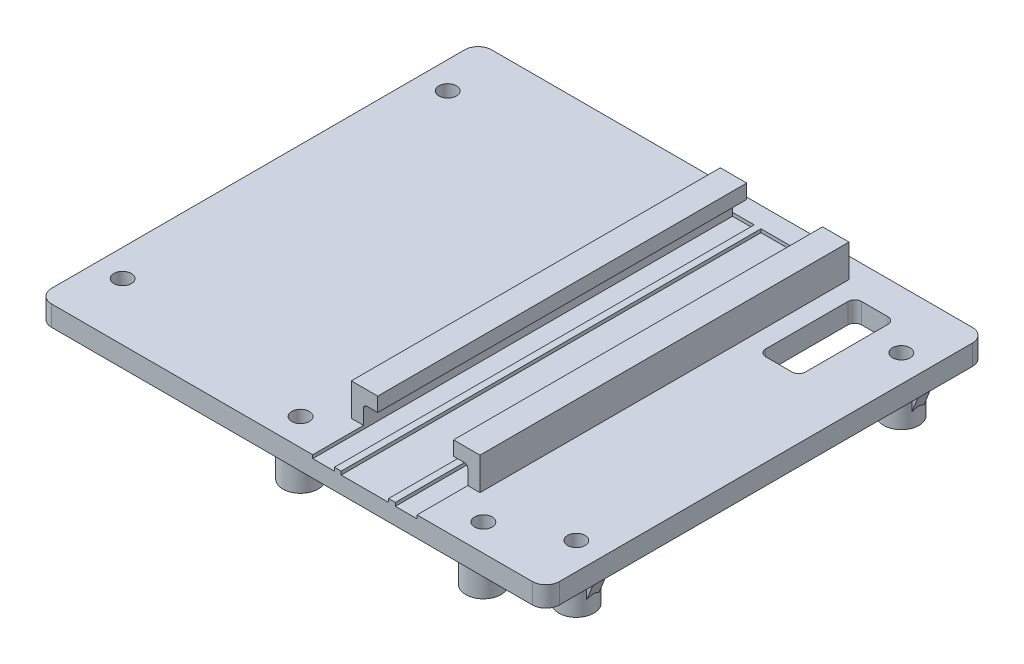
SolidWorks part; units mm, degrees
ref_plane "Alzado" through (0, 0, 0) normal (0, 0, 1) x (1, 0, 0)
ref_plane "Planta" through (0, 0, 0) normal (0, 1, 0) x (1, 0, 0)
ref_plane "Vista lateral" through (0, 0, 0) normal (1, 0, 0) x (0, 0, -1)
sketch "Croquis9" plane through (0, 0, 0) normal (0, 0, 1) x (1, 0, 0)
  line L0 (0, 17.7123) -> (0, -23.4478) construction
  line L1 (0, 10.708) -> (-22, 10.708)
  line L2 (-22, 10.708) -> (-22, 7.708)
  line L3 (-22, 7.708) -> (-19, 7.708)
  line L4 (-19, 7.708) -> (-4.5, 6.708)
  line L5 (-4.5, 6.708) -> (-4.5, -1.292)
  line L6 (-4.5, -1.292) -> (0, -1.292)
  line L7 (0, 10.708) -> (0, -1.292)
  dimension "D1" = 22
  dimension "D2" = 4.5
  dimension "D3" = 3
  dimension "D4" = 1
  dimension "D5" = 8
  dimension "D6" = 3
  dimension "D7" = 12
revolve "Revolución3" add sketch "Croquis9" angle 360 about L0
sketch "Croquis17" plane through (0, 0, 0) normal (1, 0, 0) x (0, 0, -1)
  line L0 (-4.5, -1.292) -> (4.5, -1.292) construction
  circle A0 centre (0, 4.708) radius 1.5
  dimension "D1" = 3
  dimension "D2" = 6
extrude "Cortar-Extruir7" cut sketch "Croquis17" along normal up to next
sketch "Croquis18" plane through (0, 10.708, 0) normal (0, 1, 0) x (1, 0, 0)
  line L0 (1, 2.9343) -> (1, -2.9343)
  arc A0 (1, 2.9343) -> (1, -2.9343) centre (0, 0) ccw
  dimension "D1" = 6.2
  dimension "D2" = 1
extrude "Cortar-Extruir10" cut sketch "Croquis18" against normal blind 6 from offset 3 offset against normal yes
sketch "Croquis21" plane through (0, 0, 0) normal (0, 0, 1) x (1, 0, 0)
  line L0 (0, 3.5811) -> (0, -1.3759) construction
  line L1 (0, 1.8085) -> (-3.1, 1.8085)
  line L2 (-3.1, 1.8085) -> (-3.1, -1.6716)
  line L3 (-3.1, -1.6716) -> (0, -1.6716)
  line L4 (0, 1.8085) -> (0, -1.6716)
  dimension "D1" = 3.1
revolve "Cortar-Revolución1" cut sketch "Croquis21" angle 360 about L0
chamfer "Chaflán2" distance 0.5 angle 45 1 edges at (1, 1.8085, 0)
chamfer "Chaflán1" [suppressed] distance 0.5 angle 45
sketch "Croquis22" plane through (0, 10.708, 0) normal (0, 1, 0) x (1, 0, 0)
  line L1 (-37.5, -32.5) -> (37.5, -32.5)
  line L2 (-37.5, -32.5) -> (-37.5, 32.5)
  line L3 (-37.5, 32.5) -> (37.5, 32.5)
  line L4 (37.5, -32.5) -> (37.5, 32.5)
  line L5 (-37.5, -32.5) -> (37.5, 32.5) construction
  line L6 (-37.5, 32.5) -> (37.5, -32.5) construction
  point P0 (0, 0)
  dimension "D1" = 65
  dimension "D2" = 75
extrude "Saliente-Extruir1" add sketch "Croquis22" against normal up to surface (3 mm away) up to face at (0, 7.708, 19)
fillet "Redondeo1" radius 2 4 edges at (-37.5, 9.208, -32.5) (37.5, 9.208, -32.5) (37.5, 9.208, 32.5) (-37.5, 9.208, 32.5)
sketch "Croquis23" plane through (0, 10.708, 0) normal (0, 1, 0) x (1, 0, 0)
  circle A0 centre (-33.5, 24) radius 1.3
  circle A1 centre (-33.5, -24) radius 1.3
  circle A2 centre (33.5, -24) radius 1.3
  circle A3 centre (33.5, 24) radius 1.3
  dimension "D1" = 2.6
  dimension "D4" = 48
  dimension "D3" = 33.5
  dimension "D2" = 67
  dimension "D5" = 24
extrude "Cortar-Extruir11" cut sketch "Croquis23" against normal blind 2
sketch "Croquis24" plane through (0, 10.708, 0) normal (0, 1, 0) x (1, 0, 0)
  line L1 (3.27, 29.5) -> (18.27, 29.5)
  line L2 (3.27, 29.5) -> (3.27, -32.5)
  line L3 (3.27, -32.5) -> (18.27, -32.5)
  line L4 (18.27, 29.5) -> (18.27, -32.5)
  line L5 (6.27, 29.5) -> (7.27, 29.5)
  line L6 (6.27, 29.5) -> (6.27, -32.5)
  line L7 (6.27, -32.5) -> (7.27, -32.5)
  line L8 (7.27, 29.5) -> (7.27, -32.5)
  line L9 (14.27, 29.5) -> (15.27, 29.5)
  line L10 (14.27, 29.5) -> (14.27, -32.5)
  line L11 (14.27, -32.5) -> (15.27, -32.5)
  line L12 (15.27, 29.5) -> (15.27, -32.5)
  line L13 (35.5, 32.5) -> (-35.5, 32.5) construction
  line L14 (-35.5, -32.5) -> (35.5, -32.5) construction
  dimension "D1" = 3
  dimension "D2" = 15
  dimension "D3" = 1
  dimension "D4" = 1
  dimension "D5" = 3.27
  dimension "D6" = 3
  dimension "D7" = 3
extrude "Cortar-Extruir12" cut sketch "Croquis24" against normal blind 0.5 contours L6 L1 L2 L3 | L10 L1 L8 L3 | L1 L12 L3 L4 region at (4.77, 10.708, 1.5) region at (10.77, 10.708, 1.5) region at (16.77, 10.708, 1.5)
sketch "Croquis25" plane through (0, 10.708, 0) normal (0, 1, 0) x (1, 0, 0)
  line L0 (3.27, 29.5) -> (3.27, -32.5) construction
  line L1 (18.27, 29.5) -> (18.27, -32.5) construction
  line L3 (-35.5, -32.5) -> (3.27, -32.5) construction
  circle A0 centre (-2.73, -28.5) radius 1.3
  circle A1 centre (24.27, -28.5) radius 1.3
  circle A2 centre (33.5, -24) radius 1.3 construction
  circle A3 centre (33.5, -24) radius 1.3 construction
  dimension "D2" = 6
  dimension "D1" = 6
  dimension "D4" = 4
extrude "Cortar-Extruir13" cut sketch "Croquis25" against normal blind 2
sketch "Croquis26" plane through (0, 10.708, 0) normal (0, 1, 0) x (1, 0, 0)
  line L1 (22.988, 27.6308) -> (28.8765, 27.6308)
  line L2 (22.988, 27.6308) -> (22.988, 13.4757)
  line L3 (22.988, 13.4757) -> (28.8765, 13.4757)
  line L4 (28.8765, 27.6308) -> (28.8765, 13.4757)
extrude "Cortar-Extruir14" cut sketch "Croquis26" against normal blind 10
sketch "Croquis30" plane through (0, 0, 32.5) normal (0, 0, 1) x (1, 0, 0)
  line L0 (3.27, 10.708) -> (1.27, 10.708)
  line L1 (1.27, 10.708) -> (1.27, 15.508)
  line L2 (1.27, 15.508) -> (5.17, 15.508)
  line L3 (5.17, 15.508) -> (5.17, 13.408)
  line L4 (5.17, 13.408) -> (3.27, 13.408)
  line L5 (3.27, 13.408) -> (3.27, 10.708)
  line L6 (18.27, 10.708) -> (20.27, 10.708)
  line L7 (18.27, 10.708) -> (35.5, 10.708) construction
  line L8 (20.27, 10.708) -> (20.27, 15.508)
  line L9 (20.27, 15.508) -> (16.37, 15.508)
  line L10 (16.37, 15.508) -> (16.37, 13.408)
  line L11 (16.37, 13.408) -> (18.27, 13.408)
  line L12 (18.27, 13.408) -> (18.27, 10.708)
  dimension "D1" = 1.9
  dimension "D2" = 4.8
  dimension "D3" = 2
  dimension "D4" = 2.7
extrude "Saliente-Extruir2" add sketch "Croquis30" against normal up to surface (62 mm away) from offset 7.5 up to face at (4.77, 10.458, -29.5) offset against normal yes
sketch "Croquis31" plane through (0, 0, 32.5) normal (0, 0, 1) x (1, 0, 0)
  line L0 (3.27, 13.408) -> (5.17, 13.408) construction
  line L1 (3.27, 10.208) -> (3.07, 10.208)
  line L2 (3.27, 10.208) -> (3.27, 13.408)
  line L3 (3.27, 13.408) -> (3.07, 13.408)
  line L4 (3.07, 10.208) -> (3.07, 13.408)
  line L5 (18.27, 10.208) -> (18.47, 10.208)
  line L6 (18.27, 10.208) -> (18.27, 13.408)
  line L7 (18.27, 13.408) -> (18.47, 13.408)
  line L8 (18.47, 10.208) -> (18.47, 13.408)
  line L9 (16.37, 13.408) -> (18.27, 13.408) construction
  dimension "D1" = 0.2
  dimension "D2" = 0.2
extrude "Cortar-Extruir17" cut sketch "Croquis31" against normal up to surface (62 mm away) up to face at (4.77, 10.458, -29.5)
fillet "Redondeo2" radius 0.5 2 edges at (18.47, 13.408, -2.25) (3.07, 13.408, -2.25)
fillet "Redondeo3" radius 1 4 edges at (28.8765, 9.208, -13.4757) (22.988, 9.208, -13.4757) (22.988, 9.208, -27.6308) (28.8765, 9.208, -27.6308)
sketch "Croquis33" plane through (0, 10.708, 0) normal (0, 1, 0) x (1, 0, 0)
  circle A1 centre (-33.5, -24) radius 2.6
  circle A2 centre (-33.5, 24) radius 2.6
  circle A3 centre (-2.73, -28.5) radius 2.6
  circle A4 centre (24.27, -28.5) radius 2.6
  circle A5 centre (33.5, -24) radius 2.6
  circle A6 centre (33.5, 24) radius 2.6
  dimension "D1" = 5.2
extrude "Saliente-Extruir3" add sketch "Croquis33" against normal blind 5 from surface starting at face at (25.9322, 7.708, -20.5533)
sketch "Croquis34" plane through (0, 10.708, 0) normal (0, 1, 0) x (1, 0, 0)
  circle A0 centre (-33.5, -24) radius 1.3 construction
  circle A1 centre (-2.73, -28.5) radius 1.3 construction
  circle A2 centre (24.27, -28.5) radius 1.3 construction
  circle A3 centre (33.5, -24) radius 1.3 construction
  circle A4 centre (33.5, 24) radius 1.3 construction
  circle A5 centre (-33.5, 24) radius 1.3 construction
  circle A6 centre (-33.5, -24) radius 1.3
  circle A7 centre (-2.73, -28.5) radius 1.3
  circle A8 centre (24.27, -28.5) radius 1.3
  circle A9 centre (33.5, -24) radius 1.3
  circle A10 centre (33.5, 24) radius 1.3
  circle A11 centre (-33.5, 24) radius 1.3
extrude "Cortar-Extruir18" cut sketch "Croquis34" against normal offset from surface (5 mm away) 3 up to face at (-33.5, 2.708, 21.4)
ref_axis "Eje1" through (33.5, 2.708, -24) along (0, 1, 0)
ref_plane "Plano1" through (0, 0, -24) normal (0, 0, -1) x (-1, 0, 0)
sketch "Croquis37" plane through (0, 0, -24) normal (0, 0, -1) x (-1, 0, 0)
  line L0 (-30.9, 5.208) -> (-29.9, 7.708)
  line L1 (-30.9, 2.708) -> (-30.9, 7.708) construction
  line L2 (-35.5, 7.708) -> (35.5, 7.708) construction
  dimension "D1" = 1
  dimension "D2" = 2.5
rib "Nervio3" sketch "Croquis37" sketch "Croquis37" thickness 1.8 extrusion direction parallel to sketch draft on no parameters "D1"=1.8
pattern_circular "MatrizC3" count 4 every 90 about axis through (33.5, 2.708, -24) along (0, 1, 0) of "Nervio3"
pattern_linear "MatrizL3" count 2 spacing 67.1 along (-1, 0, 0) count 2 spacing 48 along (0, 0, 1) of "MatrizC3"
